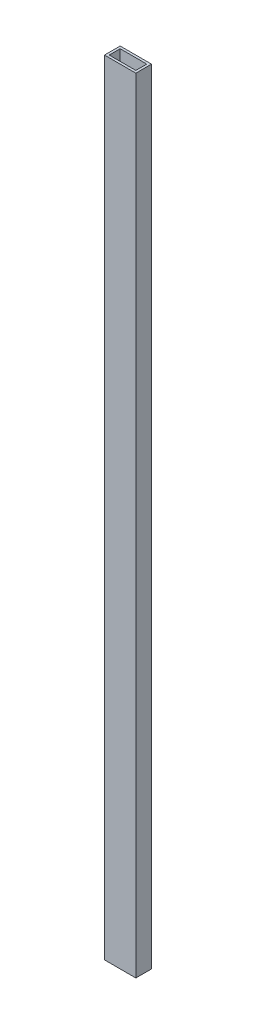
SolidWorks part; units mm, degrees
ref_plane "Спереди" through (0, 0, 0) normal (0, 0, 1) x (1, 0, 0)
ref_plane "Сверху" through (0, 0, 0) normal (0, 1, 0) x (1, 0, 0)
ref_plane "Справа" through (0, 0, 0) normal (1, 0, 0) x (0, 0, -1)
sketch "Эскиз1" plane through (0, 0, 0) normal (0, 1, 0) x (1, 0, 0)
  line L1 (-20, 10) -> (20, 10)
  line L2 (-20, 10) -> (-20, -10)
  line L3 (-20, -10) -> (20, -10)
  line L4 (20, 10) -> (20, -10)
  line L5 (-20, 10) -> (20, -10) construction
  line L6 (-20, -10) -> (20, 10) construction
  point P0 (0, 0)
  dimension "D1" = 40
  dimension "D2" = 20
extrude "Вытянуть-Тонкостенный1" add sketch "Эскиз1" along normal blind 1000 thin thin type one direction reverse wall 3
